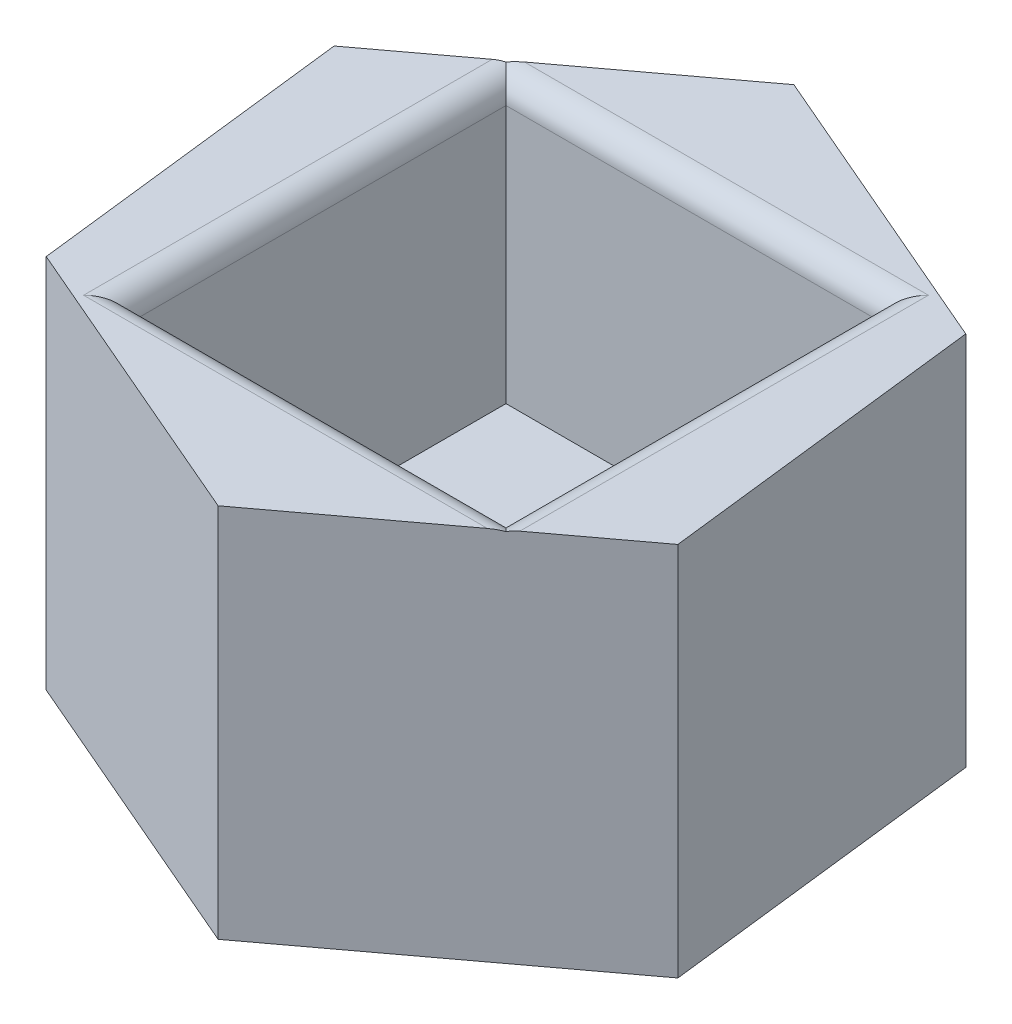
SolidWorks part; units mm, degrees
ref_plane "Front Plane" through (0, 0, 0) normal (0, 0, 1) x (1, 0, 0)
ref_plane "Top Plane" through (0, 0, 0) normal (0, 1, 0) x (1, 0, 0)
ref_plane "Right Plane" through (0, 0, 0) normal (1, 0, 0) x (0, 0, -1)
sketch "Sketch1" plane through (0, 0, 0) normal (0, 1, 0) x (1, 0, 0)
  line L1 (3.2148, -1.3838) -> (2.8058, 2.0922)
  line L2 (2.8058, 2.0922) -> (-0.409, 3.476)
  line L3 (-0.409, 3.476) -> (-3.2148, 1.3838)
  line L4 (-3.2148, 1.3838) -> (-2.8058, -2.0922)
  line L5 (-2.8058, -2.0922) -> (0.409, -3.476)
  line L6 (0.409, -3.476) -> (3.2148, -1.3838)
  circle A0 centre (0, 0) radius 3.0311 construction
  dimension "D1" = 7
extrude "Boss-Extrude1" add sketch "Sketch1" along normal blind 4
sketch "Sketch2" plane through (0, 4, 0) normal (0, 1, 0) x (1, 0, 0)
  line L1 (-2, -2) -> (2, -2)
  line L2 (-2, -2) -> (-2, 2)
  line L3 (-2, 2) -> (2, 2)
  line L4 (2, -2) -> (2, 2)
  line L5 (-2, -2) -> (2, 2) construction
  line L6 (-2, 2) -> (2, -2) construction
  circle A0 centre (0, 0) radius 1.95
  dimension "D1" = 3.9
  dimension "D2" = 4
  dimension "D3" = 4
extrude "Cut-Extrude1" cut sketch "Sketch2" against normal blind 3 contours L1 L4 L3 L2 A0 | A0 region at (-1.9943, 4, 0)
fillet "Fillet1" radius 0.25 4 edges at (0, 4, 2) (2, 4, 0) (0, 4, -2) (-2, 4, 0)
